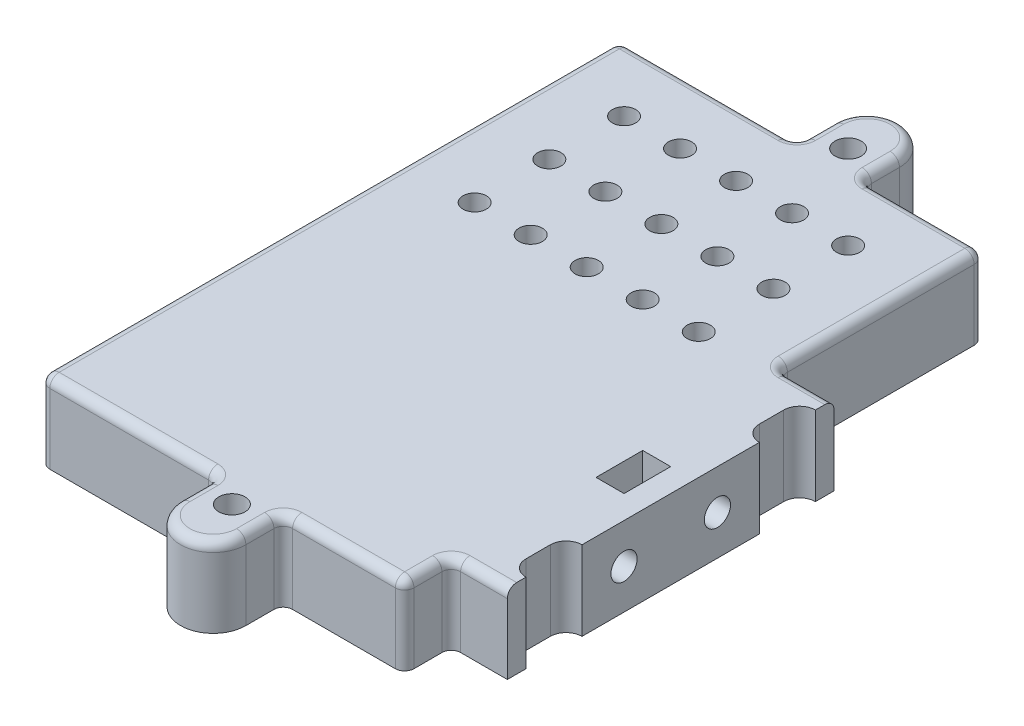
SolidWorks part; units mm, degrees
ref_plane "Front Plane" through (0, 0, 0) normal (0, 0, 1) x (1, 0, 0)
ref_plane "Top Plane" through (0, 0, 0) normal (0, 1, 0) x (1, 0, 0)
ref_plane "Right Plane" through (0, 0, 0) normal (1, 0, 0) x (0, 0, -1)
sketch "Sketch1" plane through (0, 0, 0) normal (0, 1, 0) x (1, 0, 0)
  line L0 (-14.5, -26) -> (14.5, -26) construction
  line L1 (-14.5, -26) -> (-14.5, 26) construction
  line L2 (-14.5, 26) -> (14.5, 26) construction
  line L3 (14.5, -26) -> (14.5, 26) construction
  line L4 (0, 26) -> (0, -26) construction
  line L6 (-15.5, 27) -> (15.5, 27)
  line L7 (-15.5, 27) -> (-15.5, -27)
  line L8 (-15.5, -27) -> (15.5, -27)
  line L9 (15.5, 27) -> (15.5, -27)
  line L10 (-19.5, 31) -> (19.5, 31)
  line L11 (-19.5, 31) -> (-19.5, -31)
  line L12 (-19.5, -31) -> (19.5, -31)
  line L13 (19.5, 31) -> (19.5, -31)
  point P6 (0, 0)
  point P16 (0, 31)
  point P17 (-15.5, 0)
  point P18 (-19.5, 0)
  dimension "D1" = 52
  dimension "D2" = 29
  dimension "D3" = 1
  dimension "D4" = 1
  dimension "D5" = 1
  dimension "D6" = 1
  dimension "D7" = 4
  dimension "D8" = 4
extrude "Base" add sketch "Sketch1" along normal blind 6
sketch "Sketch2" plane through (0, 6, 0) normal (0, 1, 0) x (1, 0, 0)
  line L0 (0, 31) -> (0, -31) construction
  line L1 (-19.5, 31) -> (19.5, 31)
  line L2 (-19.5, 31) -> (-19.5, -31)
  line L3 (-19.5, -31) -> (19.5, -31)
  line L4 (19.5, 31) -> (19.5, -31)
  circle A0 centre (-12, 24) radius 1.25
  circle A1 centre (-6, 24) radius 1.25
  circle A2 centre (0, 24) radius 1.25
  circle A3 centre (6, 24) radius 1.25
  circle A4 centre (12, 24) radius 1.25
  circle A5 centre (-6, 16) radius 1.25
  circle A6 centre (0, 16) radius 1.25
  circle A7 centre (6, 16) radius 1.25
  circle A8 centre (12, 16) radius 1.25
  circle A9 centre (-6, 8) radius 1.25
  circle A10 centre (0, 8) radius 1.25
  circle A11 centre (6, 8) radius 1.25
  circle A12 centre (12, 8) radius 1.25
  circle A13 centre (-12, 16) radius 1.25
  circle A14 centre (-12, 8) radius 1.25
  dimension "D1" = 2.5
  dimension "D2" = 12
  dimension "D3" = 7
  dimension "D6" = 6
  dimension "D7" = 8
  dimension "D4" = 5
  dimension "D5" = 3
extrude "Top Cover" add sketch "Sketch2" along normal blind 2.5
sketch "Sketch3" plane through (0, 0, 0) normal (0, 1, 0) x (1, 0, 0)
  line L0 (-0.5, 31) -> (6.5, 31)
  line L1 (19.5, 31) -> (-19.5, 31) construction
  line L2 (-19.5, 0) -> (19.5, 0) construction
  line L3 (-19.5, 31) -> (-19.5, -31) construction
  line L4 (19.5, -31) -> (19.5, 31) construction
  line L5 (-0.5, 31) -> (-0.5, 35)
  line L6 (6.5, 31) -> (6.5, 35)
  line L7 (-0.5, -31) -> (-0.5, -35)
  line L8 (-0.5, -31) -> (6.5, -31)
  line L9 (6.5, -31) -> (6.5, -35)
  circle A0 centre (3, 33) radius 1.4
  arc A1 (-0.5, 35) -> (6.5, 35) centre (3, 35) cw
  circle A2 centre (3, -33) radius 1.4
  arc A3 (-0.5, -35) -> (6.5, -35) centre (3, -35) ccw
  point P10 (3, 31)
  dimension "D2" = 33
  dimension "D3" = 2.8
  dimension "D4" = 4
  dimension "D1" = 7
  dimension "D5" = 3
extrude "Mounting Ends" add sketch "Sketch3" along normal up to surface (8.5 mm away) up to face at (-12, 8.5, -14.75)
sketch "Sketch5" plane through (0, 0, 0) normal (0, 1, 0) x (1, 0, 0)
  line L0 (19.5, -26) -> (25.5, -26)
  line L1 (19.5, -31) -> (19.5, 31) construction
  line L3 (25.5, 9) -> (19.5, 9)
  line L4 (6.5, -31) -> (19.5, -31) construction
  line L5 (25.5, -26) -> (25.5, -24)
  line L6 (25.5, -18) -> (25.5, 1)
  line L7 (23.8, -19.7) -> (23.8, -22.3)
  line L8 (25.5, 9) -> (25.5, 7)
  line L9 (23.8, 2.7) -> (23.8, 5.3)
  line L10 (19.5, 9) -> (19.5, -26)
  arc A0 (23.8, -22.3) -> (25.5, -24) centre (25.5, -22.3) ccw
  arc A1 (23.8, -19.7) -> (25.5, -18) centre (25.5, -19.7) cw
  arc A2 (23.8, 2.7) -> (25.5, 1) centre (25.5, 2.7) ccw
  arc A3 (23.8, 5.3) -> (25.5, 7) centre (25.5, 5.3) cw
  point P21 (23.8, 4)
  point P22 (23.8, -21)
  dimension "D4" = 1.7
  dimension "D1" = 6
  dimension "D2" = 5
  dimension "D3" = 35
  dimension "D5" = 6
  dimension "D6" = 2.6
  dimension "D7" = 2.6
  dimension "D8" = 25
  dimension "D9" = 2
extrude "Basket Mounting Edge" add sketch "Sketch5" along normal up to surface (8.5 mm away) up to face at (-12, 8.5, -14.75)
sketch "Sketch6" plane through (25.5, 0, 0) normal (1, 0, 0) x (0, 0, -1)
  line L0 (-18, 4.25) -> (1, 4.25) construction
  line L1 (-18, 8.5) -> (-18, 0) construction
  line L2 (1, 8.5) -> (1, 0) construction
  line L3 (-8.5, 8.5) -> (-8.5, 0) construction
  line L4 (-18, 8.5) -> (1, 8.5) construction
  line L5 (-18, 0) -> (1, 0) construction
  circle A0 centre (-13.5, 4.25) radius 1.4
  circle A1 centre (-3.5, 4.25) radius 1.4
  dimension "D1" = 2.8
  dimension "D2" = 4.5
extrude "Basket Clamp Screw Holes" cut sketch "Sketch6" against normal blind 8
fillet "1mm Edge Fillets" radius 1 22 edges at (13, 8.5, -31) (-10, 8.5, 31) (-0.5, 8.5, -33) (6.5, 8.5, 33) (3, 8.5, -38.5) (3, 8.5, 38.5) (6.5, 8.5, -33) (-0.5, 8.5, 33) (19.5, 8.5, 28.5) (-19.5, 8.5, 0) (-19.5, 4.25, 31) (-0.5, 4.25, 31) (6.5, 4.25, 31) (19.5, 4.25, 31) (19.5, 4.25, -31) (6.5, 4.25, -31) (-0.5, 4.25, -31) (-19.5, 4.25, -31) (22.5, 8.5, -9) (22.5, 8.5, 26) (19.5, 4.25, -9) (19.5, 4.25, 26)
sketch "Sketch7" plane through (0, 8.5, 0) normal (0, 1, 0) x (1, 0, 0)
  line L0 (25.5, -18) -> (25.5, 1) construction
  line L1 (20, -6) -> (23, -6)
  line L2 (20, -6) -> (20, -11)
  line L3 (20, -11) -> (23, -11)
  line L4 (23, -6) -> (23, -11)
  point P6 (25.5, -8.5)
  point P7 (23, -8.5)
  dimension "D1" = 2.5
  dimension "D2" = 3
  dimension "D3" = 5
extrude "Zip Tie Hole" cut sketch "Sketch7" against normal through all
